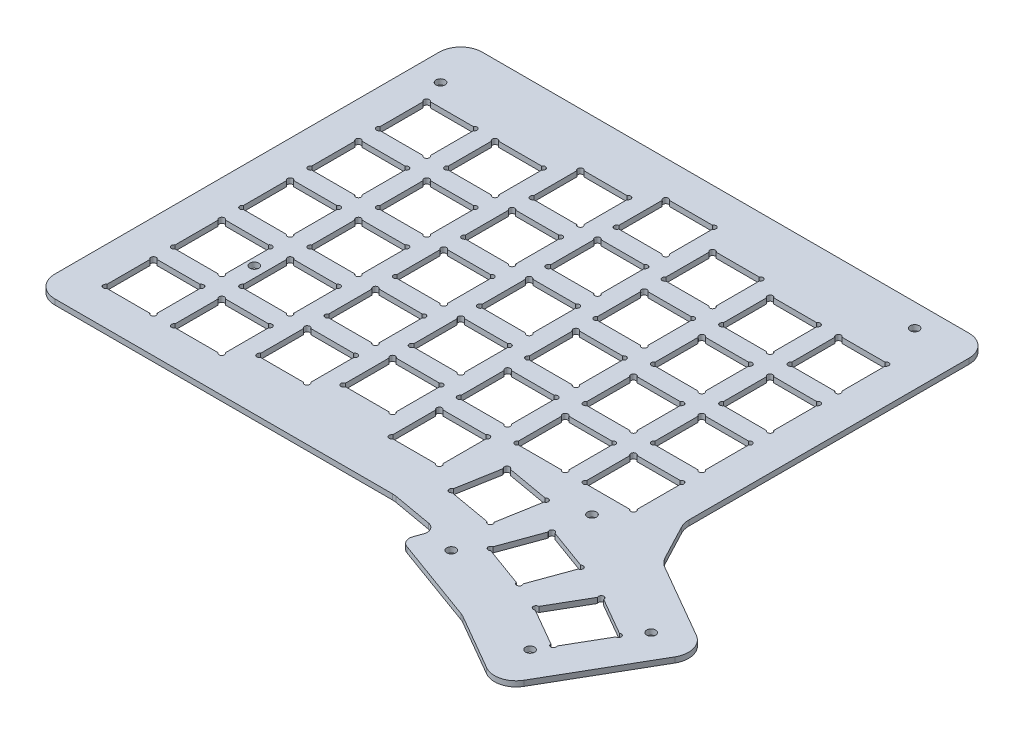
SolidWorks part; units mm, degrees
ref_plane "Front Plane" through (0, 0, 0) normal (0, 0, 1) x (1, 0, 0)
ref_plane "Top Plane" through (0, 0, 0) normal (0, 1, 0) x (1, 0, 0)
ref_plane "Right Plane" through (0, 0, 0) normal (1, 0, 0) x (0, 0, -1)
sketch "Sketch1" plane through (0, 0, 0) normal (0, 1, 0) x (1, 0, 0)
  line L0 (-119.7491, 121.9513) -> (28.0509, 121.9513)
  line L3 (34.6603, 23.8288) -> (62.1795, 7.9406)
  line L4 (62.1795, 7.9406) -> (40.7734, -29.1359)
  line L5 (40.7734, -29.1359) -> (19.4145, -16.8044)
  line L6 (19.4145, -16.8044) -> (-7.217, -7.1113)
  line L7 (-7.217, -7.1113) -> (-4.5567, 0.1977)
  line L8 (-4.5567, 0.1977) -> (-19.0389, 2.7513)
  line L9 (-19.0389, 2.7513) -> (-119.7491, 2.7513)
  line L10 (-119.7491, 2.7513) -> (-119.7491, 121.9513)
  line L11 (-18.7764, 5.7513) -> (-112.5491, 5.7513) construction
  line L12 (34.6603, 23.8288) -> (28.0509, 36.3869)
  line L13 (28.0509, 36.3869) -> (28.0509, 121.9513)
  line L14 (35.7381, -22.7647) -> (20.6865, -14.0747) construction
  line L15 (28.8016, 30.5418) -> (32.8015, 22.9418) construction
  line L16 (-116.7491, 9.9513) -> (-116.7491, 114.7513) construction
  line L17 (55.9445, 3.1411) -> (41.567, -21.7614) construction
  line L18 (-112.5491, 118.9513) -> (21.8509, 118.9513) construction
  line L19 (29.0509, 23.7513) -> (54.6509, 8.8513) construction
  line L20 (25.0509, 115.7513) -> (25.0509, 31.3513) construction
  line L21 (25.0509, 31.3513) -> (29.0509, 23.7513) construction
  line L29 (20.6865, -14.0747) -> (0.2509, -6.6487) construction
  dimension "D9" = 3
  dimension "D4" = 3
  dimension "D7" = 20
  dimension "D5" = 10
  dimension "D8" = 30
  dimension "D3" = 3
  dimension "D2" = 3
  dimension "D10" = 3
  dimension "D11" = 3
  dimension "D6" = 3
  dimension "D12" = 3
  dimension "D13" = 3
  dimension "D14" = 5
  dimension "D15" = 3
extrude "Boss-Extrude1" add sketch "Sketch1" against normal blind 1.5
sketch "Sketch2" plane through (0, 0, 0) normal (0, 1, 0) x (1, 0, 0)
  line L0 (-38.8611, 112.2513) -> (-52.8611, 98.2513) construction
  line L1 (-52.8611, 112.2513) -> (-38.8611, 112.2513)
  line L2 (-52.8611, 112.2513) -> (-52.8611, 98.2513)
  line L3 (-52.8611, 98.2513) -> (-38.8611, 98.2513)
  line L4 (-38.8611, 112.2513) -> (-38.8611, 98.2513)
  line L5 (-52.8611, 112.2513) -> (-38.8611, 98.2513) construction
  line L6 (28.0509, 121.9513) -> (-119.7491, 121.9513) construction
  line L7 (-119.7491, 121.9513) -> (-119.7491, 2.7513) construction
  line L8 (-52.8611, 112.2513) -> (-53.0379, 112.4281) construction
  line L9 (-52.5076, 111.8978) -> (-52.8611, 111.2363) construction
  line L10 (-52.5076, 111.8978) -> (-51.8461, 112.2513) construction
  circle A0 centre (-39.2147, 111.8978) radius 0.75
  circle A1 centre (-52.5076, 111.8978) radius 0.75
  circle A2 centre (-52.6843, 98.4281) radius 0.75
  circle A3 centre (-39.2147, 98.6049) radius 0.75
  dimension "D5" = 1.5
  dimension "D7" = 1.5
  dimension "D9" = 1.5
  dimension "D11" = 1.5
  dimension "D1" = 14
  dimension "D3" = 9.7
  dimension "D2" = 66.888
  dimension "D4" = 0.5
  dimension "D6" = 0.5
  dimension "D8" = 0.25
  dimension "D10" = 0.5
extrude "Cut-Extrude1" cut sketch "Sketch2" against normal blind 10 contours A3 L4 A0 L1 A1 L2 A2 L3 | A1 | A0 | A3 | A2 region at (-45.8723, 0, -105.2402)
sketch "Sketch3" plane through (0, 0, 0) normal (0, 1, 0) x (1, 0, 0)
  line L0 (-39.8761, 112.2513) -> (-51.8461, 112.2513) construction
  line L1 (-71.9112, 107.4888) -> (-57.9111, 107.4888)
  line L2 (-71.9112, 107.4888) -> (-71.9112, 93.4887)
  line L3 (-71.9112, 93.4887) -> (-57.9111, 93.4887)
  line L4 (-57.9111, 107.4888) -> (-57.9111, 93.4887)
  line L5 (-71.9112, 107.4888) -> (-57.9111, 93.4887) construction
  line L7 (-57.9111, 107.4888) -> (-71.9112, 93.4887) construction
  line L8 (-52.8611, 105.1967) -> (-38.8611, 105.2513) construction
  line L9 (-52.8611, 111.2363) -> (-52.8611, 99.157) construction
  line L10 (-38.8611, 111.2363) -> (-38.8611, 99.2663) construction
  circle A0 centre (-58.2646, 107.1353) radius 0.75
  circle A1 centre (-71.5576, 107.1353) radius 0.75
  circle A2 centre (-71.5576, 93.8423) radius 0.75
  circle A3 centre (-58.2646, 93.8423) radius 0.75
  point P6 (-45.8611, 112.2513)
  point P7 (-64.9111, 107.4888)
  dimension "D7" = 1.5
  dimension "D9" = 1.5
  dimension "D4" = 0.5
  dimension "D6" = 0.5
  dimension "D8" = 1.5
  dimension "D10" = 1.5
  dimension "D1" = 19.05
  dimension "D2" = 4.7625
  dimension "D3" = 0.5
  dimension "D5" = 0.5
sketch "Sketch4" plane through (0, 0, 0) normal (0, 1, 0) x (1, 0, 0)
  line L0 (-39.8761, 112.2513) -> (-51.8461, 112.2513) construction
  line L1 (-90.9612, 102.7263) -> (-76.9611, 102.7263)
  line L2 (-90.9612, 102.7263) -> (-90.9612, 88.7262)
  line L3 (-90.9612, 88.7262) -> (-76.9611, 88.7262)
  line L4 (-76.9611, 102.7263) -> (-76.9611, 88.7262)
  line L5 (-57.9111, 107.4888) -> (-57.9111, 93.4887) construction
  line L6 (-90.9612, 102.7263) -> (-76.9611, 88.7262) construction
  line L7 (-76.9611, 102.7263) -> (-90.9612, 88.7262) construction
  line L8 (-52.8611, 105.1967) -> (-38.8611, 105.2513) construction
  line L9 (-52.8611, 111.2363) -> (-52.8611, 99.157) construction
  line L10 (-38.8611, 111.2363) -> (-38.8611, 99.2663) construction
  circle A0 centre (-77.3146, 102.3728) radius 0.75
  circle A1 centre (-90.6076, 102.3728) radius 0.75
  circle A2 centre (-90.6076, 89.0798) radius 0.75
  circle A3 centre (-77.3146, 89.0798) radius 0.75
  dimension "D7" = 1.5
  dimension "D9" = 1.5
  dimension "D4" = 0.5
  dimension "D6" = 0.5
  dimension "D8" = 1.5
  dimension "D10" = 1.5
  dimension "D3" = 0.5
  dimension "D5" = 0.5
  dimension "D1" = 9.525
  dimension "D2" = 19.05
sketch "Sketch5" plane through (0, 0, 0) normal (0, 1, 0) x (1, 0, 0)
  line L0 (-39.8761, 112.2513) -> (-51.8461, 112.2513) construction
  line L1 (-110.0112, 102.7263) -> (-96.0111, 102.7263)
  line L2 (-110.0112, 102.7263) -> (-110.0112, 88.7262)
  line L3 (-110.0112, 88.7262) -> (-96.0111, 88.7262)
  line L4 (-96.0111, 102.7263) -> (-96.0111, 88.7262)
  line L5 (-76.9611, 102.7263) -> (-76.9611, 88.7262) construction
  line L6 (-110.0112, 102.7263) -> (-96.0111, 88.7262) construction
  line L8 (-96.0111, 102.7263) -> (-110.0112, 88.7262) construction
  line L9 (-52.8611, 105.1967) -> (-38.8611, 105.2513) construction
  line L10 (-52.8611, 111.2363) -> (-52.8611, 99.157) construction
  line L11 (-38.8611, 111.2363) -> (-38.8611, 99.2663) construction
  circle A0 centre (-109.6576, 102.3728) radius 0.75
  circle A1 centre (-96.3646, 102.3728) radius 0.75
  circle A2 centre (-96.3646, 89.0798) radius 0.75
  circle A3 centre (-109.6576, 89.0798) radius 0.75
  dimension "D7" = 1.5
  dimension "D9" = 1.5
  dimension "D4" = 0.5
  dimension "D6" = 0.5
  dimension "D8" = 1.5
  dimension "D10" = 1.5
  dimension "D1" = 19.05
  dimension "D3" = 0.5
  dimension "D5" = 0.5
  dimension "D2" = 9.525
sketch "Sketch6" plane through (0, 0, 0) normal (0, 1, 0) x (1, 0, 0)
  line L0 (-39.8761, 112.2513) -> (-51.8461, 112.2513) construction
  line L1 (-33.8111, 106.2513) -> (-19.811, 106.2513)
  line L2 (-33.8111, 106.2513) -> (-33.8111, 92.2512)
  line L3 (-33.8111, 92.2512) -> (-19.811, 92.2512)
  line L4 (-19.811, 106.2513) -> (-19.811, 92.2512)
  line L5 (-52.8611, 111.2363) -> (-52.8611, 99.157) construction
  line L6 (-33.8111, 106.2513) -> (-19.811, 92.2512) construction
  line L7 (-19.811, 106.2513) -> (-33.8111, 92.2512) construction
  line L8 (-52.8611, 105.1967) -> (-38.8611, 105.2513) construction
  line L9 (-52.8611, 111.2363) -> (-52.8611, 99.157) construction
  line L10 (-38.8611, 111.2363) -> (-38.8611, 99.2663) construction
  circle A0 centre (-33.4576, 105.8978) radius 0.75
  circle A1 centre (-20.1646, 105.8978) radius 0.75
  circle A2 centre (-33.4576, 92.6048) radius 0.75
  circle A3 centre (-20.1646, 92.6048) radius 0.75
  dimension "D7" = 1.5
  dimension "D9" = 1.5
  dimension "D4" = 0.5
  dimension "D6" = 0.5
  dimension "D8" = 1.5
  dimension "D10" = 1.5
  dimension "D3" = 0.5
  dimension "D5" = 0.5
  dimension "D2" = 19.05
  dimension "D1" = 6
sketch "Sketch7" plane through (0, 0, 0) normal (0, 1, 0) x (1, 0, 0)
  line L0 (-39.8761, 112.2513) -> (-51.8461, 112.2513) construction
  line L1 (-14.7611, 103.2513) -> (-0.761, 103.2513)
  line L2 (-14.7611, 103.2513) -> (-14.7611, 89.2512)
  line L3 (-14.7611, 89.2512) -> (-0.761, 89.2512)
  line L4 (-0.761, 103.2513) -> (-0.761, 89.2512)
  line L5 (-33.8111, 106.2513) -> (-33.8111, 92.2512) construction
  line L6 (-14.7611, 103.2513) -> (-0.761, 89.2512) construction
  line L7 (-0.761, 103.2513) -> (-14.7611, 89.2512) construction
  line L8 (-52.8611, 105.1967) -> (-38.8611, 105.2513) construction
  line L9 (-52.8611, 111.2363) -> (-52.8611, 99.157) construction
  line L10 (-38.8611, 111.2363) -> (-38.8611, 99.2663) construction
  circle A0 centre (-14.4076, 102.8978) radius 0.75
  circle A1 centre (-1.1146, 102.8978) radius 0.75
  circle A2 centre (-1.1146, 89.6048) radius 0.75
  circle A3 centre (-14.4076, 89.6048) radius 0.75
  dimension "D7" = 1.5
  dimension "D9" = 1.5
  dimension "D4" = 0.5
  dimension "D6" = 0.5
  dimension "D8" = 1.5
  dimension "D10" = 1.5
  dimension "D3" = 0.5
  dimension "D5" = 0.5
  dimension "D2" = 19.05
  dimension "D1" = 9
sketch "Sketch8" plane through (0, 0, 0) normal (0, 1, 0) x (1, 0, 0)
  line L0 (-39.8761, 112.2513) -> (-51.8461, 112.2513) construction
  line L1 (4.2889, 103.2513) -> (18.289, 103.2513)
  line L2 (4.2889, 103.2513) -> (4.2889, 89.2512)
  line L3 (4.2889, 89.2512) -> (18.289, 89.2512)
  line L4 (18.289, 103.2513) -> (18.289, 89.2512)
  line L5 (-14.7611, 103.2513) -> (-14.7611, 89.2512) construction
  line L6 (4.2889, 103.2513) -> (18.289, 89.2512) construction
  line L7 (18.289, 103.2513) -> (4.2889, 89.2512) construction
  line L8 (-52.8611, 105.1967) -> (-38.8611, 105.2513) construction
  line L9 (-52.8611, 111.2363) -> (-52.8611, 99.157) construction
  line L10 (-38.8611, 111.2363) -> (-38.8611, 99.2663) construction
  circle A0 centre (4.6424, 102.8978) radius 0.75
  circle A1 centre (17.9354, 102.8978) radius 0.75
  circle A2 centre (17.9354, 89.6048) radius 0.75
  circle A3 centre (4.6424, 89.6048) radius 0.75
  dimension "D7" = 1.5
  dimension "D9" = 1.5
  dimension "D4" = 0.5
  dimension "D6" = 0.5
  dimension "D8" = 1.5
  dimension "D10" = 1.5
  dimension "D1" = 19.05
  dimension "D3" = 0.5
  dimension "D5" = 0.5
  dimension "D2" = 9
extrude "Cut-Extrude2" cut sketch "Sketch3" against normal blind 10 contours L1 L4 L3 L2 | A0 | A1 | A2 | A3
extrude "Cut-Extrude3" cut sketch "Sketch4" against normal blind 10 contours A3 L4 A0 L1 A1 L2 A2 L3 | A0 | A1 | A2 | A3 region at (-83.9611, 0, -95.7263)
extrude "Cut-Extrude4" cut sketch "Sketch5" against normal blind 10 contours A3 L3 A2 L4 A1 L1 A0 L2 | A1 | A0 | A3 | A2 region at (-103.0111, 0, -95.7263)
extrude "Cut-Extrude5" cut sketch "Sketch6" against normal blind 10 contours L1 L4 L3 L2 | A0 | A1 | A2 | A3
extrude "Cut-Extrude6" cut sketch "Sketch7" against normal blind 10 contours L1 L4 L3 L2 | A0 | A1 | A3 | A2
extrude "Cut-Extrude7" cut sketch "Sketch8" against normal blind 10 contours L2 A0 L1 | L1 L4 L3 L2 | A1 | A3 | A2 | A0 region at (4.797, 0, -102.7432)
pattern_linear "LPattern1" count 5 spacing 19.05 along (0, 0, 1) of "Cut-Extrude5", "Cut-Extrude1", "Cut-Extrude2", "Cut-Extrude3", "Cut-Extrude4"
pattern_linear "LPattern2" count 4 spacing 19.05 along (0, 0, 1) of "Cut-Extrude7", "Cut-Extrude6"
sketch "Sketch10" plane through (0, 0, 0) normal (0, 1, 0) x (1, 0, 0)
  line L0 (-35.8111, 32.0513) -> (-17.8111, 32.0513) construction
  line L1 (-17.8111, 32.0513) -> (-17.8111, 14.0513) construction
  line L2 (-17.8111, 14.0513) -> (-35.8111, 14.0513) construction
  line L3 (-35.8111, 14.0513) -> (-35.8111, 32.0513) construction
  line L4 (-16.7611, 48.1013) -> (1.2389, 48.1013) construction
  line L5 (1.2389, 48.1013) -> (1.2389, 30.1013) construction
  line L6 (1.2389, 30.1013) -> (-16.7611, 30.1013) construction
  line L7 (-16.7611, 30.1013) -> (-16.7611, 48.1013) construction
  line L8 (-32.7961, 30.0513) -> (-20.826, 30.0513) construction
  line L9 (-33.8111, 29.0363) -> (-33.8111, 17.0662) construction
  line L10 (-13.7461, 46.1013) -> (-1.776, 46.1013) construction
  line L11 (-14.7611, 45.0863) -> (-14.7611, 33.1162) construction
  line L12 (-10.0631, 25.2844) -> (3.7243, 22.8533)
  line L13 (-10.0631, 25.2844) -> (-12.4942, 11.497)
  line L14 (3.7243, 22.8533) -> (1.2932, 9.0659)
  line L15 (-12.4942, 11.497) -> (1.2932, 9.0659)
  line L16 (-10.0631, 25.2844) -> (1.2932, 9.0659) construction
  line L17 (3.7243, 22.8533) -> (-12.4942, 11.497) construction
  line L18 (-52.8611, 105.1967) -> (-38.8611, 105.2513) construction
  line L19 (-52.8611, 111.2363) -> (-52.8611, 99.157) construction
  line L21 (-32.7961, 16.0512) -> (-20.826, 16.0512) construction
  line L22 (-38.8611, 111.2363) -> (-38.8611, 99.2663) construction
  line L23 (-14.8111, 9.8747) -> (-11.6854, 27.6013) construction
  line L24 (-11.6854, 27.6013) -> (6.0411, 24.4756) construction
  line L25 (6.0411, 24.4756) -> (2.9155, 6.7491) construction
  line L26 (2.9155, 6.7491) -> (-14.8111, 9.8747) construction
  line L27 (-11.2787, 18.3907) -> (-13.2482, 18.738) construction
  line L28 (-3.1694, 24.0689) -> (-2.8221, 26.0384) construction
  circle A0 centre (-9.7763, 24.8748) radius 0.75
  circle A1 centre (3.3147, 22.5665) radius 0.75
  circle A2 centre (-12.0846, 11.7838) radius 0.75
  circle A3 centre (1.0064, 9.4755) radius 0.75
  point P10 (-26.8111, 30.0513)
  point P11 (-26.8111, 32.0513)
  point P14 (-33.8111, 23.0513)
  point P15 (-35.8111, 23.0513)
  point P18 (-7.7611, 46.1013)
  point P19 (-7.7611, 48.1013)
  point P22 (-14.7611, 39.1013)
  point P23 (-16.7611, 39.1013)
  dimension "D11" = 1.5
  dimension "D10" = 0.5
  dimension "D6" = 2.5
  dimension "D1" = 18
  dimension "D2" = 10
  dimension "D3" = 90
  dimension "D4" = 90
  dimension "D5" = 3
  dimension "D7" = 0.5
  dimension "D8" = 0.5
  dimension "D9" = 0.5
extrude "Cut-Extrude8" cut sketch "Sketch10" against normal blind 10 contours L12 L14 L15 L13 | A0 | A1 | A2 | A3
sketch "Sketch11" plane through (0, 0, 0) normal (0, 1, 0) x (1, 0, 0)
  line L4 (12.0244, 23.0041) -> (28.9388, 16.8477) construction
  line L5 (12.0244, 23.0041) -> (2.7898, -2.3676) construction
  line L6 (28.9388, 16.8477) -> (19.7043, -8.524) construction
  line L7 (2.7898, -2.3676) -> (19.7043, -8.524) construction
  line L8 (11.6806, 16.2121) -> (20.0481, -1.732) construction
  line L9 (24.8364, 11.4238) -> (6.8923, 3.0563) construction
  line L10 (-11.6854, 27.6013) -> (6.0411, 24.4756) construction
  line L11 (6.0411, 24.4756) -> (2.9155, 6.7491) construction
  line L12 (2.9155, 6.7491) -> (-14.8111, 9.8747) construction
  line L13 (-14.8111, 9.8747) -> (-11.6854, 27.6013) construction
  line L14 (-9.0635, 25.1082) -> (2.7247, 23.0296) construction
  line L15 (-10.2394, 24.2849) -> (-12.318, 12.4966) construction
  line L16 (-3.1694, 24.0689) -> (-2.8221, 26.0384) construction
  line L17 (-11.2787, 18.3907) -> (-13.2482, 18.738) construction
  line L18 (-52.8611, 105.1967) -> (-38.8611, 105.2513) construction
  line L19 (-52.8611, 111.2363) -> (-52.8611, 99.157) construction
  line L20 (11.6806, 16.2121) -> (24.8364, 11.4238)
  line L21 (24.8364, 11.4238) -> (20.0481, -1.732)
  line L22 (20.0481, -1.732) -> (6.8923, 3.0563)
  line L23 (6.8923, 3.0563) -> (11.6806, 16.2121)
  line L24 (-32.7961, 16.0512) -> (-20.826, 16.0512) construction
  line L25 (9.2864, 9.6342) -> (7.4071, 10.3182) construction
  line L26 (18.2585, 13.818) -> (20.4816, 19.9259) construction
  line L32 (-38.8611, 111.2363) -> (-38.8611, 99.2663) construction
  line L39 (2.7898, -2.3676) -> (19.7043, -8.524) construction
  circle A0 centre (11.8919, 15.759) radius 0.75
  circle A1 centre (24.3832, 11.2125) radius 0.75
  circle A2 centre (19.8367, -1.2788) radius 0.75
  circle A3 centre (7.3454, 3.2676) radius 0.75
  arc A4 (3.548, 21.8538) -> (2.7247, 23.0296) centre (3.3147, 22.5665) ccw construction
  dimension "D1" = 18
  dimension "D4" = 90
  dimension "D2" = 90
  dimension "D3" = 90
  dimension "D5" = 20
  dimension "D6" = 90
  dimension "D7" = 90
  dimension "D8" = 27
  dimension "D9" = 3
  dimension "D10" = 27
  dimension "D11" = 0.5
  dimension "D12" = 0.5
  dimension "D13" = 0.5
  dimension "D14" = 0.5
sketch "Sketch12" plane through (0, 0, 0) normal (0, 1, 0) x (1, 0, 0)
  line L0 (34.5054, 7.2036) -> (46.6298, 0.2035)
  line L1 (46.6298, 0.2035) -> (39.6298, -11.9209)
  line L2 (39.6298, -11.9209) -> (27.5053, -4.9209)
  line L3 (27.5053, -4.9209) -> (34.5054, 7.2036)
  line L5 (34.5054, 7.2036) -> (39.6298, -11.9209) construction
  line L6 (-119.7491, 2.7513) -> (-19.0389, 2.7513) construction
  line L7 (2.7898, -2.3676) -> (19.7043, -8.524) construction
  line L8 (19.7043, -8.524) -> (100.0637, -37.7724) construction
  line L9 (22.5234, -9.55) -> (36.0234, 13.8326)
  line L10 (36.0234, 13.8326) -> (51.6118, 4.8326)
  line L11 (51.6118, 4.8326) -> (38.1118, -18.55)
  line L12 (38.1118, -18.55) -> (22.5234, -9.55)
  line L13 (40.5676, 3.7035) -> (43.8176, 9.3326) construction
  line L14 (31.0054, 1.1413) -> (29.2734, 2.1413) construction
  line L15 (28.9388, 16.8477) -> (19.7043, -8.524) construction
  line L16 (12.0244, 23.0041) -> (28.9388, 16.8477) construction
  line L17 (46.6298, 0.2035) -> (27.5053, -4.9209) construction
  line L18 (-52.8611, 105.1967) -> (-38.8611, 105.2513) construction
  line L19 (-52.8611, 111.2363) -> (-52.8611, 99.157) construction
  line L20 (-38.8611, 111.2363) -> (-38.8611, 99.2663) construction
  circle A0 centre (34.6348, 6.7206) radius 0.75
  circle A1 centre (46.1469, 0.0741) radius 0.75
  circle A2 centre (39.5004, -11.438) radius 0.75
  circle A3 centre (27.9883, -4.7915) radius 0.75
  arc A4 (0.2936, 9.2422) -> (1.4695, 10.0655) centre (1.0064, 9.4755) ccw construction
  dimension "D6" = 0.5
  dimension "D5" = 0.5
  dimension "D3" = 90
  dimension "D7" = 0.5
  dimension "D8" = 0.5
  dimension "D1" = 30
  dimension "D2" = 90
  dimension "D4" = 3
extrude "Cut-Extrude10" cut sketch "Sketch11" against normal blind 10 contours L20 L21 L22 L23 | A0 | A1 | A3 | A2
extrude "Cut-Extrude11" cut sketch "Sketch12" against normal blind 10 contours L0 L1 L2 L3 | A0 | A1 | A3 | A2
fillet "Fillet5" radius 6 9 edges at (28.0509, -0.75, -36.3869) (34.6603, -0.75, -23.8288) (62.1795, -0.75, -7.9406) (40.7734, -0.75, 29.1359) (19.4145, -0.75, 16.8044) (-19.0389, -0.75, -2.7513) (-119.7491, -0.75, -2.7513) (-119.7491, -0.75, -121.9513) (28.0509, -0.75, -121.9513)
fillet "Fillet6" radius 2.5 2 edges at (-4.5567, -0.75, -0.1977) (-7.217, -0.75, 7.1113)
sketch "Sketch50" plane through (0, -1.5, 0) normal (0, -1, 0) x (-1, 0, 0)
  circle A0 centre (112.2491, 108.8174) radius 1.25
  circle A3 centre (-13.2509, 115.5513) radius 1.25
  circle A5 centre (93.9491, 38.5853) radius 1.25
  circle A9 centre (-13.2509, 25.5513) radius 1.25
  circle A11 centre (-50.0169, 5.3013) radius 1.25
  circle A13 centre (-37.2509, -15.6987) radius 1.25
  circle A15 centre (-2.2669, -2.6987) radius 1.25
  dimension "D1" = 2.5
  dimension "D4" = 2.5
  dimension "D6" = 2.5
  dimension "D10" = 2.5
  dimension "D12" = 2.5
  dimension "D14" = 2.5
  dimension "D16" = 2.5
extrude "Cut-Extrude18" cut sketch "Sketch50" against normal blind 10
equation "\"EDGE_PAD\"=3"
equation "\"LAYER_SWITCH_THICKNESS\"= 1.5"
equation "\"D1@Boss-Extrude1\"=\"LAYER_SWITCH_THICKNESS\""
equation "\"CUTOUT_SIZE\"= 14"
equation "\"D1@Sketch2\"=\"CUTOUT_SIZE\""
equation "\"D2@Sketch2\"=\"EDGE_PAD\"+63.888"
equation "\"D3@Sketch2\"=\"EDGE_PAD\"+6.7"
equation "\"CASE_THICKNESS\"= 3"
equation "\"SCREW_SIZE\"= 2.5"
equation "\"OUTER_SCREW_SIZE\"=2.5"
equation "\"D1@Sketch50\"=\"OUTER_SCREW_SIZE\""
equation "\"D4@Sketch50\"=\"OUTER_SCREW_SIZE\""
equation "\"D6@Sketch50\"=\"OUTER_SCREW_SIZE\""
equation "\"D10@Sketch50\"=\"OUTER_SCREW_SIZE\""
equation "\"D12@Sketch50\"=\"OUTER_SCREW_SIZE\""
equation "\"D14@Sketch50\"=\"OUTER_SCREW_SIZE\""
equation "\"D16@Sketch50\"=\"OUTER_SCREW_SIZE\""
equation "\"EDGE_CIRCLES\"= 1.5"
equation "\"EDGE_CIRCLES_OFFSET\"= 0.5"
equation "\"D4@Sketch2\"=\"EDGE_CIRCLES_OFFSET\""
equation "\"D5@Sketch2\"=\"EDGE_CIRCLES\""
equation "\"D6@Sketch2\"=\"EDGE_CIRCLES_OFFSET\""
equation "\"D7@Sketch2\"=\"EDGE_CIRCLES\""
equation "\"D10@Sketch2\"=\"EDGE_CIRCLES_OFFSET\""
equation "\"D11@Sketch2\"=\"EDGE_CIRCLES\""
equation "\"D9@Sketch2\"=\"EDGE_CIRCLES\""
equation "\"D3@Sketch3\"=\"EDGE_CIRCLES_OFFSET\""
equation "\"D4@Sketch3\"=\"EDGE_CIRCLES_OFFSET\""
equation "\"D5@Sketch3\"=\"EDGE_CIRCLES_OFFSET\""
equation "\"D6@Sketch3\"=\"EDGE_CIRCLES_OFFSET\""
equation "\"D7@Sketch3\"=\"EDGE_CIRCLES\""
equation "\"D8@Sketch3\"=\"EDGE_CIRCLES\""
equation "\"D9@Sketch3\"=\"EDGE_CIRCLES\""
equation "\"D10@Sketch3\"=\"EDGE_CIRCLES\""
equation "\"D3@Sketch4\"=\"EDGE_CIRCLES_OFFSET\""
equation "\"D4@Sketch4\"=\"EDGE_CIRCLES_OFFSET\""
equation "\"D5@Sketch4\"=\"EDGE_CIRCLES_OFFSET\""
equation "\"D6@Sketch4\"=\"EDGE_CIRCLES_OFFSET\""
equation "\"D7@Sketch4\"=\"EDGE_CIRCLES\""
equation "\"D8@Sketch4\"=\"EDGE_CIRCLES\""
equation "\"D9@Sketch4\"=\"EDGE_CIRCLES\""
equation "\"D10@Sketch4\"=\"EDGE_CIRCLES\""
equation "\"D3@Sketch5\"=\"EDGE_CIRCLES_OFFSET\""
equation "\"D4@Sketch5\"=\"EDGE_CIRCLES_OFFSET\""
equation "\"D5@Sketch5\"=\"EDGE_CIRCLES_OFFSET\""
equation "\"D6@Sketch5\"=\"EDGE_CIRCLES_OFFSET\""
equation "\"D7@Sketch5\"=\"EDGE_CIRCLES\""
equation "\"D8@Sketch5\"=\"EDGE_CIRCLES\""
equation "\"D9@Sketch5\"=\"EDGE_CIRCLES\""
equation "\"D10@Sketch5\"=\"EDGE_CIRCLES\""
equation "\"D3@Sketch6\"=\"EDGE_CIRCLES_OFFSET\""
equation "\"D4@Sketch6\"=\"EDGE_CIRCLES_OFFSET\""
equation "\"D5@Sketch6\"=\"EDGE_CIRCLES_OFFSET\""
equation "\"D6@Sketch6\"=\"EDGE_CIRCLES_OFFSET\""
equation "\"D7@Sketch6\"=\"EDGE_CIRCLES\""
equation "\"D8@Sketch6\"=\"EDGE_CIRCLES\""
equation "\"D9@Sketch6\"=\"EDGE_CIRCLES\""
equation "\"D10@Sketch6\"=\"EDGE_CIRCLES\""
equation "\"D3@Sketch7\"=\"EDGE_CIRCLES_OFFSET\""
equation "\"D4@Sketch7\"=\"EDGE_CIRCLES_OFFSET\""
equation "\"D5@Sketch7\"=\"EDGE_CIRCLES_OFFSET\""
equation "\"D6@Sketch7\"=\"EDGE_CIRCLES_OFFSET\""
equation "\"D7@Sketch7\"=\"EDGE_CIRCLES\""
equation "\"D8@Sketch7\"=\"EDGE_CIRCLES\""
equation "\"D9@Sketch7\"=\"EDGE_CIRCLES\""
equation "\"D10@Sketch7\"=\"EDGE_CIRCLES\""
equation "\"D3@Sketch8\"=\"EDGE_CIRCLES_OFFSET\""
equation "\"D4@Sketch8\"=\"EDGE_CIRCLES_OFFSET\""
equation "\"D5@Sketch8\"=\"EDGE_CIRCLES_OFFSET\""
equation "\"D6@Sketch8\"=\"EDGE_CIRCLES_OFFSET\""
equation "\"D7@Sketch8\"=\"EDGE_CIRCLES\""
equation "\"D8@Sketch8\"=\"EDGE_CIRCLES\""
equation "\"D9@Sketch8\"=\"EDGE_CIRCLES\""
equation "\"D10@Sketch8\"=\"EDGE_CIRCLES\""
equation "\"D7@Sketch10\"=\"EDGE_CIRCLES_OFFSET\""
equation "\"D8@Sketch10\"=\"EDGE_CIRCLES_OFFSET\""
equation "\"D9@Sketch10\"=\"EDGE_CIRCLES_OFFSET\""
equation "\"D10@Sketch10\"=\"EDGE_CIRCLES_OFFSET\""
equation "\"D11@Sketch10\"=\"EDGE_CIRCLES\""
equation "\"D11@Sketch11\"=\"EDGE_CIRCLES_OFFSET\""
equation "\"D12@Sketch11\"=\"EDGE_CIRCLES_OFFSET\""
equation "\"D13@Sketch11\"=\"EDGE_CIRCLES_OFFSET\""
equation "\"D14@Sketch11\"=\"EDGE_CIRCLES_OFFSET\""
equation "\"D5@Sketch12\"=\"EDGE_CIRCLES_OFFSET\""
equation "\"D6@Sketch12\"=\"EDGE_CIRCLES_OFFSET\""
equation "\"D7@Sketch12\"=\"EDGE_CIRCLES_OFFSET\""
equation "\"D8@Sketch12\"=\"EDGE_CIRCLES_OFFSET\""
equation "\"D15@Sketch1\"=\"EDGE_PAD\""
equation "\"D3@Sketch1\"=\"EDGE_PAD\""
equation "\"D9@Sketch1\"=\"EDGE_PAD\""
equation "\"D10@Sketch1\"=\"EDGE_PAD\""
equation "\"D11@Sketch1\"=\"EDGE_PAD\""
equation "\"D12@Sketch1\"=\"EDGE_PAD\""
equation "\"D6@Sketch1\"=\"EDGE_PAD\""
equation "\"D13@Sketch1\"=\"EDGE_PAD\""
equation "\"D14@Sketch1\"=\"EDGE_PAD\"+2"
equation "\"D2@Sketch1\"=\"EDGE_PAD\""
equation "\"D4@Sketch1\"=\"EDGE_PAD\""
